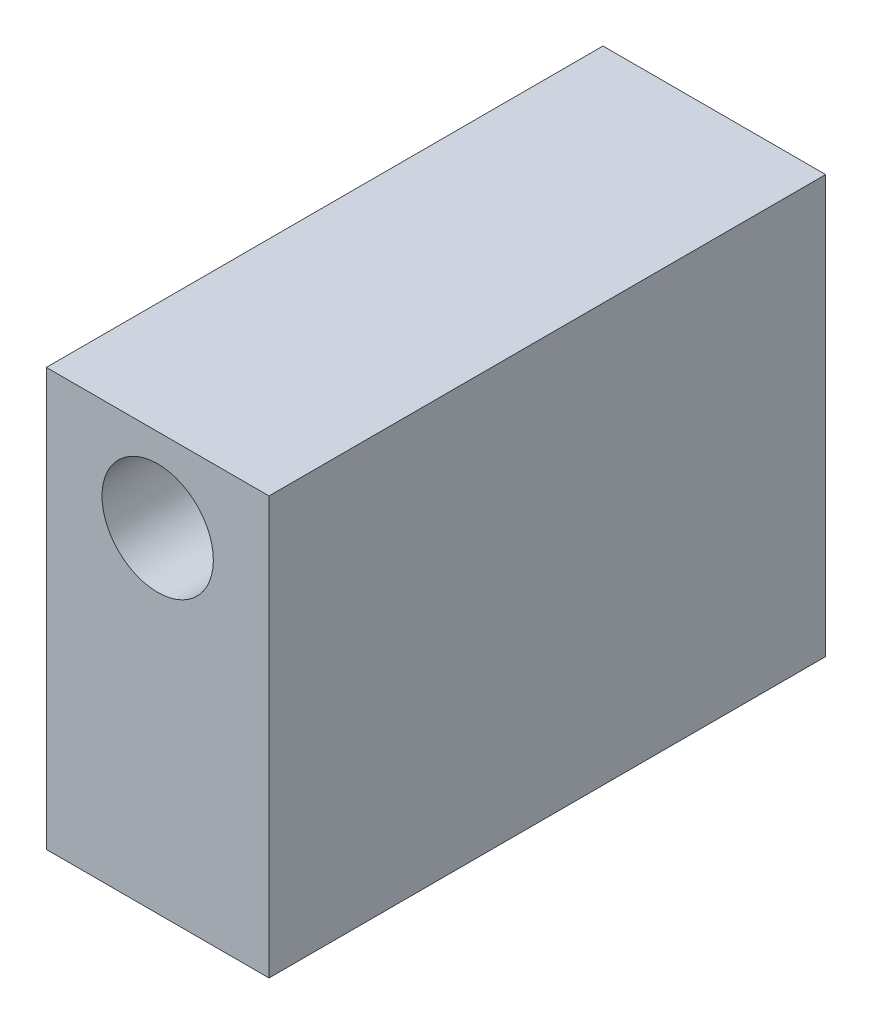
SolidWorks part; units mm, degrees
ref_plane "Front Plane" through (0, 0, 0) normal (0, 0, 1) x (1, 0, 0)
ref_plane "Top Plane" through (0, 0, 0) normal (0, 1, 0) x (1, 0, 0)
ref_plane "Right Plane" through (0, 0, 0) normal (1, 0, 0) x (0, 0, -1)
sketch "Sketch1" plane through (0, 0, 0) normal (0, 1, 0) x (1, 0, 0)
  line L1 (-20, 50) -> (20, 50)
  line L2 (-20, 50) -> (-20, -50)
  line L3 (-20, -50) -> (20, -50)
  line L4 (20, 50) -> (20, -50)
  line L5 (-20, 50) -> (20, -50) construction
  line L6 (-20, -50) -> (20, 50) construction
  point P0 (0, 0)
  dimension "D1" = 40
  dimension "D2" = 100
extrude "Boss-Extrude1" add sketch "Sketch1" along normal blind 75
sketch "Sketch2" plane through (0, 0, 0) normal (0, 0, 1) x (1, 0, 0)
  line L0 (0, 75) -> (0, 60) construction
  line L1 (-20, 75) -> (20, 75) construction
  circle A0 centre (0, 60) radius 10
  dimension "D2" = 20
  dimension "D1" = 15
extrude "Cut-Extrude1" cut sketch "Sketch2" against normal blind 50 and the other way blind 50
ref_axis "Axis1" through (0, 60, 50) along (0, 0, -1)
ref_axis "Axis2" through (0, 78.75, 0) along (0, -1, 0)
